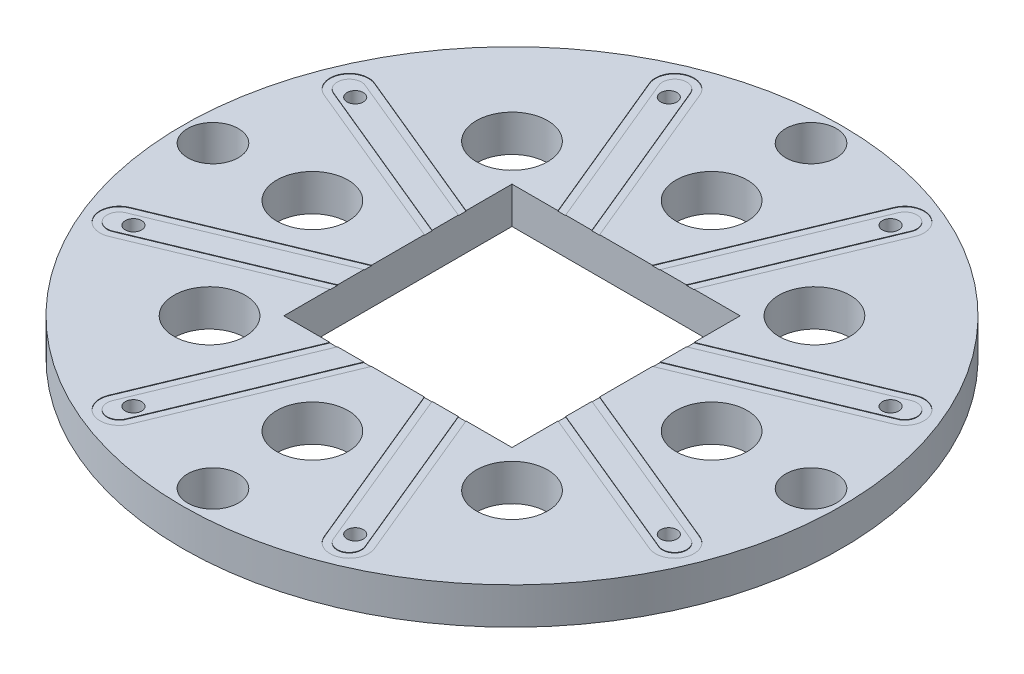
SolidWorks part; units mm, degrees
material "Ceramic Porcelain"
ref_plane "Front Plane" through (0, 0, 0) normal (0, 0, 1) x (1, 0, 0)
ref_plane "Top Plane" through (0, 0, 0) normal (0, 1, 0) x (1, 0, 0)
ref_plane "Right Plane" through (0, 0, 0) normal (1, 0, 0) x (0, 0, -1)
ref_axis "Y Axis" through (0, 0.0762, 0) along (0, -1, 0)
sketch "Boday Sketch" plane through (0, 0, 0) normal (0, 1, 0) x (1, 0, 0)
  circle A0 centre (0, 0) radius 11.557
  dimension "D1" = 23.114
extrude "Body" add sketch "Boday Sketch" against normal blind 1.27
sketch "Copper Sketch" plane through (0, 0, 0) normal (0, 1, 0) x (1, 0, 0)
  circle A0 centre (0, 0) radius 11.557
  dimension "D1" = 23.114
extrude "Copper" add sketch "Copper Sketch" along normal blind 0.0175
sketch "Screw Position" plane through (0, 0, 0) normal (0, 1, 0) x (1, 0, 0)
  point P0 (0, 10.541)
  dimension "D1" = 10.541
sketch "IO Hole Positions" plane through (0, 0, 0) normal (0, 1, 0) x (1, 0, 0)
  point P0 (-3.8881, 9.3866)
  point P1 (3.8881, 9.3866)
  point P5 (9.3866, 3.8881)
  point P6 (9.3866, -3.8881)
  point P7 (3.8881, -9.3866)
  point P8 (-3.8881, -9.3866)
  point P9 (-9.3866, -3.8881)
  point P10 (-9.3866, 3.8881)
  point P11 (0, 0)
  dimension "D2" = 8
sketch "Gap" plane through (0, 0, 0) normal (0, 1, 0) x (1, 0, 0)
  line L1 (0.6236, 0.2583) -> (-3.4102, 9.9969)
  line L2 (-4.6575, 9.4803) -> (-0.6236, -0.2583)
  line L3 (-0.6236, -0.2583) -> (0.6236, 0.2583)
  arc A0 (-3.4102, 9.9969) -> (-4.6575, 9.4803) centre (-4.0339, 9.7386) ccw
  point P0 (0.6236, 0.2583)
sketch "Center Sketch" plane through (0, 0, 0) normal (0, 1, 0) x (1, 0, 0)
  line L0 (0.3926, 0.1626) -> (-3.6412, 9.9013)
  line L1 (-4.4265, 9.576) -> (-0.3926, -0.1626)
  line L2 (-0.3926, -0.1626) -> (0.3926, 0.1626)
  arc A0 (-3.6412, 9.9013) -> (-4.4265, 9.576) centre (-4.0339, 9.7386) ccw
  point P0 (0.3926, 0.1626)
  point P3 (-3.6412, 9.9013)
  dimension "D1" = 0.425
hole_wizard "#0 Clearance Hole1" positions "Sketch23" profile "Sketch24" hole size "#0" standard "ANSI Inch" end condition through all
sketch "Sketch23" plane through (0, 0.0175, 0) normal (0, 1, 0) x (-1, 0, 0)
  point P0 (0, -10.4865)
sketch "Sketch24" plane through (0, 0.0175, -10.4865) normal (1, 0, 0) x (0, 0, 1)
  line L0 (0, 0) -> (0, 1.2875)
  line L1 (0, 1.2875) -> (0.889, 1.2875)
  line L2 (0.889, 1.2875) -> (0.889, 0)
  line L5 (0.889, 0) -> (0, 0)
  line L11 (0, -6.35) -> (0, 107.95) construction
  dimension "Thru Hole Dia." = 1.778
  dimension "Thru Hole Depth" = 1.2875
pattern_circular "Screw Holes" count 4 over 360 about axis through (0, 0.0762, 0) along (0, -1, 0) of "#0 Clearance Hole1"
extrude "Gap Cut" cut sketch "Gap" along normal through all
extrude "Center" add sketch "Center Sketch" along normal blind 0.0175 separate body
sketch "IO Hole Sketch" plane through (0, 0, 0) normal (0, 1, 0) x (1, 0, 0)
  circle A0 centre (-3.8881, 9.3866) radius 0.287
  dimension "D1" = 0.574
extrude "IO Hole" cut sketch "IO Hole Sketch" against normal through all and the other way through all
pattern_circular "Gap Cuts" count 8 over 360 about axis through (0, 0.0762, 0) along (0, -1, 0) of "Gap Cut"
pattern_circular "Centers" count 8 over 360 about axis through (0, 0.0762, 0) along (0, -1, 0) of "Center"
pattern_circular "IO Holes" count 8 over 360 about axis through (0, 0.0762, 0) along (0, -1, 0) of "IO Hole"
sketch "Pocket Sketch" plane through (0, 0, 0) normal (0, 1, 0) x (1, 0, 0)
  line L1 (-4, -4) -> (4, -4)
  line L2 (-4, -4) -> (-4, 4)
  line L3 (-4, 4) -> (4, 4)
  line L4 (4, -4) -> (4, 4)
  line L5 (-4, -4) -> (4, 4) construction
  line L6 (-4, 4) -> (4, -4) construction
  point P0 (0, 0)
  dimension "D2" = 8
  dimension "D1" = 8
extrude "Pocket" cut sketch "Pocket Sketch" against normal through all and the other way through all
sketch "Posts" plane through (0, 0, 0) normal (0, 1, 0) x (1, 0, 0)
  circle A0 centre (0, 7) radius 1.25
  circle A8 centre (-5.3033, 5.3033) radius 1.25
  point P0 (0, 7)
  point P4 (-5.3033, 5.3033)
  dimension "D2" = 2.5
  dimension "D4" = 2.5
  dimension "D1" = 7
  dimension "D3" = 7.5
extrude "Post Cut" cut sketch "Posts" against normal through all and the other way through all
pattern_circular "Post Cuts" count 4 over 360 about axis through (0, 0.0762, 0) along (0, -1, 0) of "Post Cut"
equation "\"mount_d\"= 0.91in"
equation "\"dieletric_h\"= 0.05in"
equation "\"D1@Boday Sketch\" = \"mount_d\""
equation "\"D1@Body\" = \"dieletric_h\""
equation "\"screw_inner_r\"= 0.415in"
equation "\"io_r\"= 0.4in"
equation "\"D1@Screw Position\" = \"screw_inner_r\""
equation "\"D1@IO Hole Positions\" = \"io_r\""
equation "\"io_hole_d\"= 0.574mm"
equation "\"D1@IO Hole Sketch\" = \"io_hole_d\""
equation "\"W\"= 0.85mm"
equation "\"G\"= 0.25mm"
equation "\"copper_t\"= 17.5um"
equation "\"D1@Gap\"=\"W\" / 2 + \"G\""
equation "\"silicon_size\"= 8mm"
equation "\"D1@Center\" = \"copper_t\""
equation "\"D1@Copper\"=\"copper_t\""
equation "\"D1@Pocket Sketch\" = \"silicon_size\""
equation "\"D2@Pocket Sketch\" = \"silicon_size\""
equation "\"post_r1\"= 7mm"
equation "\"post_r2\" = 7.5mm"
equation "\"D1@Posts\"=\"post_r1\""
equation "\"post_size\"= 2.5mm"
equation "\"D2@Posts\"=\"post_size\""
equation "\"D3@Posts\"=\"post_r2\""
equation "\"D4@Posts\"=\"post_size\""
